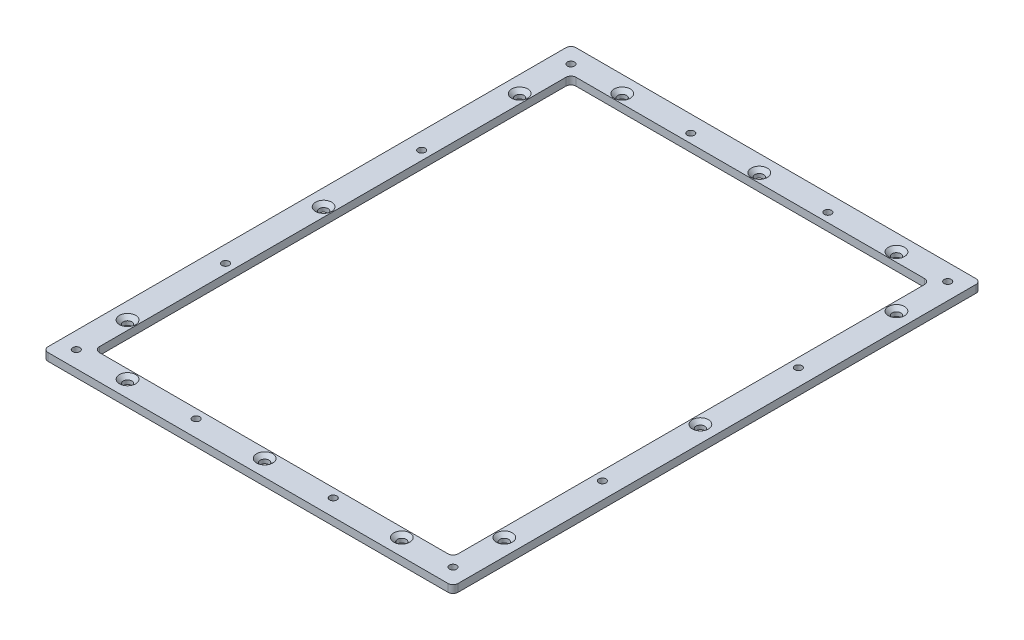
SolidWorks part; units mm, degrees
ref_plane "Front Plane" through (0, 0, 0) normal (0, 0, 1) x (1, 0, 0)
ref_plane "Top Plane" through (0, 0, 0) normal (0, 1, 0) x (1, 0, 0)
ref_plane "Right Plane" through (0, 0, 0) normal (1, 0, 0) x (0, 0, -1)
sketch "Sketch1" plane through (0, 0, 0) normal (0, 1, 0) x (1, 0, 0)
  line L0 (78, 103) -> (-78, 103) construction
  line L1 (-70, -93) -> (70, -93)
  line L2 (-70, -93) -> (-70, 93)
  line L3 (-70, 93) -> (70, 93)
  line L4 (70, -93) -> (70, 93)
  line L5 (-70, -93) -> (70, 93) construction
  line L6 (-70, 93) -> (70, -93) construction
  line L7 (80, -103) -> (-80, -103)
  line L8 (80, -103) -> (80, 103)
  line L9 (80, 103) -> (-80, 103)
  line L10 (-80, -103) -> (-80, 103)
  line L11 (80, -103) -> (-80, 103) construction
  line L12 (80, 103) -> (-80, -103) construction
  line L13 (-80, 101) -> (-80, -101) construction
  point P0 (0, 0)
  point P5 (0, 0)
  dimension "D1" = 10
  dimension "D2" = 10
extrude "Boss-Extrude1" add sketch "Sketch1" along normal blind 3
ref_axis "Axis2" through (0, -0.675, 0) along (0, 1, 0)
fillet "Fillet1" radius 2 8 edges at (80, 1.5, -103) (80, 1.5, 103) (-80, 1.5, -103) (-80, 1.5, 103) (70, 1.5, -93) (70, 1.5, 93) (-70, 1.5, 93) (-70, 1.5, -93)
ref_plane "Plane1" through (78, 0, 0) normal (-1, 0, 0) x (0, 0, 1)
sketch "Sketch6" plane through (0, 0, 0) normal (0, -1, 0) x (1, 0, 0)
  line L9 (-78, -102) -> (78, -102)
  line L10 (79, -101) -> (79, 101)
  line L11 (78, 102) -> (-78, 102)
  line L12 (-79, 101) -> (-79, -101)
  line L13 (-78, -102) -> (78, -102)
  line L14 (79, -101) -> (79, 101)
  line L15 (78, 102) -> (-78, 102)
  line L16 (-79, 101) -> (-79, -101)
  line L21 (-78, -101.5) -> (78, -101.5)
  line L22 (78.5, -101) -> (78.5, 101)
  line L23 (78, 101.5) -> (-78, 101.5)
  line L24 (-78.5, 101) -> (-78.5, -101)
  line L25 (-78, -101.5) -> (78, -101.5)
  line L26 (78.5, -101) -> (78.5, 101)
  line L27 (78, 101.5) -> (-78, 101.5)
  line L28 (-78.5, 101) -> (-78.5, -101)
  arc A8 (78, -102) -> (79, -101) centre (78, -101) ccw
  arc A9 (79, 101) -> (78, 102) centre (78, 101) ccw
  arc A10 (-78, 102) -> (-79, 101) centre (-78, 101) ccw
  arc A11 (-79, -101) -> (-78, -102) centre (-78, -101) ccw
  arc A12 (78, -102) -> (79, -101) centre (78, -101) ccw
  arc A13 (79, 101) -> (78, 102) centre (78, 101) ccw
  arc A14 (-78, 102) -> (-79, 101) centre (-78, 101) ccw
  arc A15 (-79, -101) -> (-78, -102) centre (-78, -101) ccw
  arc A20 (78, -101.5) -> (78.5, -101) centre (78, -101) ccw
  arc A21 (78, -101.5) -> (78.5, -101) centre (78, -101) ccw
  arc A22 (78.5, 101) -> (78, 101.5) centre (78, 101) ccw
  arc A23 (78.5, 101) -> (78, 101.5) centre (78, 101) ccw
  arc A24 (-78, 101.5) -> (-78.5, 101) centre (-78, 101) ccw
  arc A25 (-78, 101.5) -> (-78.5, 101) centre (-78, 101) ccw
  arc A26 (-78.5, -101) -> (-78, -101.5) centre (-78, -101) ccw
  arc A27 (-78.5, -101) -> (-78, -101.5) centre (-78, -101) ccw
  dimension "D1" = 1
  dimension "D2" = 1.5
extrude "Boss-Extrude3" add sketch "Sketch6" along normal blind 0.5
fillet "Fillet2" radius 0.25 32 edges at (-79, -0.5, 0) (-78.7071, -0.5, 101.7071) (0, -0.5, 102) (78.7071, -0.5, 101.7071) (79, -0.5, 0) (78.7071, -0.5, -101.7071) (0, -0.5, -102) (-78.5, -0.5, 0) (-78.3536, -0.5, 101.3536) (0, -0.5, 101.5) (78.3536, -0.5, 101.3536) (78.5, -0.5, 0) (78.3536, -0.5, -101.3536) (0, -0.5, -101.5) (-78.3536, 0, -101.3536) (-78.5, 0, 0) (-78.3536, 0, 101.3536) (0, 0, 101.5) (78.3536, 0, 101.3536) (78.5, 0, 0) (78.3536, 0, -101.3536) (-78.7071, 0, -101.7071) (-79, 0, 0) (-78.7071, 0, 101.7071) (0, 0, 102) (78.7071, 0, 101.7071) (79, 0, 0) (78.7071, 0, -101.7071) (-78.7071, -0.5, -101.7071) (-78.3536, -0.5, -101.3536) (0, 0, -101.5) (0, 0, -102)
sketch "Sketch10" plane through (0, 3, 0) normal (0, 1, 0) x (1, 0, 0)
  line L0 (-53.5, 96.5) -> (0, 96.5) construction
  line L1 (0, 96.5) -> (53.5, 96.5) construction
  line L2 (-73.5, 76.5) -> (-73.5, 0) construction
  line L3 (-73.5, 0) -> (-73.5, -76.5) construction
  line L4 (-53.5, -96.5) -> (0, -96.5) construction
  line L5 (0, -96.5) -> (53.5, -96.5) construction
  line L6 (73.5, 76.5) -> (73.5, 0) construction
  line L7 (73.5, 0) -> (73.5, -76.5) construction
  line L8 (-73.5, 76.5) -> (-73.5, 96.5) construction
  line L9 (-73.5, 96.5) -> (-53.5, 96.5) construction
  line L10 (0, 0) -> (0, 43.7963) construction
  line L11 (0, 0) -> (39.7562, 0) construction
  circle A0 centre (0, 96.5) radius 1.7 construction
  circle A1 centre (-53.5, 96.5) radius 1.7 construction
  circle A2 centre (-73.5, 76.5) radius 1.7 construction
  circle A3 centre (-73.5, 0) radius 1.7 construction
  circle A4 centre (-73.5, -76.5) radius 1.7 construction
  circle A5 centre (-53.5, -96.5) radius 1.7 construction
  circle A6 centre (0, -96.5) radius 1.7 construction
  circle A7 centre (53.5, -96.5) radius 1.7 construction
  circle A8 centre (73.5, -76.5) radius 1.7 construction
  circle A9 centre (73.5, 0) radius 1.7 construction
  circle A10 centre (73.5, 76.5) radius 1.7 construction
  circle A11 centre (53.5, 96.5) radius 1.7 construction
  circle A12 centre (0, 96.5) radius 1.7
  circle A13 centre (-53.5, 96.5) radius 1.7
  circle A14 centre (-73.5, 76.5) radius 1.7
  circle A15 centre (-73.5, 0) radius 1.7
  circle A16 centre (-73.5, -76.5) radius 1.7
  circle A17 centre (-53.5, -96.5) radius 1.7
  circle A18 centre (0, -96.5) radius 1.7
  circle A19 centre (53.5, -96.5) radius 1.7
  circle A20 centre (73.5, -76.5) radius 1.7
  circle A21 centre (73.5, 0) radius 1.7
  circle A22 centre (73.5, 76.5) radius 1.7
  circle A23 centre (53.5, 96.5) radius 1.7
  circle A24 centre (73.5, -38.25) radius 1.4
  circle A25 centre (73.5, 38.25) radius 1.4
  circle A26 centre (26.75, 96.5) radius 1.4
  circle A27 centre (-26.75, 96.5) radius 1.4
  circle A28 centre (-73.5, 38.25) radius 1.4
  circle A29 centre (-73.5, -38.25) radius 1.4
  circle A30 centre (-26.75, -96.5) radius 1.4
  circle A31 centre (26.75, -96.5) radius 1.4
  circle A32 centre (-73.5, 96.5) radius 1.4
  circle A33 centre (73.5, 96.5) radius 1.4
  circle A34 centre (73.5, -96.5) radius 1.4
  circle A35 centre (-73.5, -96.5) radius 1.4
  dimension "D1" = 2.8
extrude "Cut-Extrude1" cut sketch "Sketch10" against normal through all
hole_wizard "CSK for M3 Flat Head Machine Screw2" positions "3DSketch3" profile "Sketch11" countersink size "M3" standard "ANSI Metric" end condition through all
sketch3d "3DSketch3"
  line L0 (-53.5, 0, -96.5) -> (-53.5, 3, -96.5) construction
  line L1 (0, 0, -96.5) -> (0, 3, -96.5) construction
  line L2 (-73.5, 0, -76.5) -> (-73.5, 3, -76.5) construction
  line L3 (53.5, 0, -96.5) -> (53.5, 3, -96.5) construction
  line L4 (73.5, 0, -76.5) -> (73.5, 3, -76.5) construction
  line L5 (73.5, 0, 0) -> (73.5, 3, 0) construction
  line L6 (73.5, 0, 76.5) -> (73.5, 3, 76.5) construction
  line L7 (53.5, 0, 96.5) -> (53.5, 3, 96.5) construction
  line L8 (0, 0, 96.5) -> (0, 3, 96.5) construction
  line L9 (-53.5, 0, 96.5) -> (-53.5, 3, 96.5) construction
  line L10 (-73.5, 0, 76.5) -> (-73.5, 3, 76.5) construction
  line L11 (-73.5, 0, 0) -> (-73.5, 3, 0) construction
  point P0 (-53.5, 3, -96.5)
  point P4 (0, 3, -96.5)
  point P8 (-73.5, 3, -76.5)
  point P12 (53.5, 3, -96.5)
  point P16 (73.5, 3, -76.5)
  point P20 (73.5, 3, 0)
  point P28 (53.5, 3, 96.5)
  point P32 (0, 3, 96.5)
  point P36 (-53.5, 3, 96.5)
  point P40 (-73.5, 3, 76.5)
  point P44 (73.5, 3, 76.5)
  point P46 (-73.5, 3, 0)
sketch "Sketch11" plane through (-53.5, 3, -96.5) normal (1, 0, 0) x (0, 0, 1)
  line L0 (0, 0) -> (0, 3.5)
  line L1 (0, 3.5) -> (1.725, 3.5)
  line L2 (1.7, 3.475) -> (1.7, 1.45)
  line L3 (1.7, 1.45) -> (3.15, 0)
  line L5 (3.15, 0) -> (0, 0)
  line L6 (-1.7, 1.45) -> (-3.15, 0) construction
  line L7 (1.725, 3.5) -> (1.7, 3.475)
  line L8 (-1.725, 3.5) -> (-1.7, 3.475) construction
  line L11 (0, -6.35) -> (0, 107.95) construction
  dimension "Thru Hole Dia." = 3.4
  dimension "Thru Hole Depth" = 3.5
  dimension "Near C'Sink Dia." = 6.3
  dimension "Near C'Sink Angle" = 90
  dimension "Far C'Sink Dia." = 3.45
  dimension "Far C'Sink Angle" = 90
sketch "Sketch12" plane through (0, 0, 0) normal (0, -1, 0) x (1, 0, 0)
  line L0 (78, -102.25) -> (-78, -102.25) construction
  line L1 (79.25, 101) -> (79.25, -101) construction
  line L2 (-79.25, -101) -> (-79.25, 101) construction
  line L3 (-78, 102.25) -> (78, 102.25) construction
  line L4 (78, -102.25) -> (-78, -102.25)
  line L5 (79.25, 101) -> (79.25, -101)
  line L6 (-79.25, -101) -> (-79.25, 101)
  line L7 (-78, 102.25) -> (78, 102.25)
  line L9 (-249.5654, 283.7441) -> (249.5654, 283.7441)
  line L10 (-249.5654, 283.7441) -> (-249.5654, -283.7441)
  line L11 (-249.5654, -283.7441) -> (249.5654, -283.7441)
  line L12 (249.5654, 283.7441) -> (249.5654, -283.7441)
  line L13 (-249.5654, 283.7441) -> (249.5654, -283.7441) construction
  line L14 (-249.5654, -283.7441) -> (249.5654, 283.7441) construction
  arc A0 (-79.25, -101) -> (-78, -102.25) centre (-78, -101) ccw construction
  arc A1 (78, -102.25) -> (79.25, -101) centre (78, -101) ccw construction
  arc A2 (79.25, 101) -> (78, 102.25) centre (78, 101) ccw construction
  arc A3 (-78, 102.25) -> (-79.25, 101) centre (-78, 101) ccw construction
  arc A4 (-79.25, -101) -> (-78, -102.25) centre (-78, -101) ccw
  arc A5 (78, -102.25) -> (79.25, -101) centre (78, -101) ccw
  arc A6 (79.25, 101) -> (78, 102.25) centre (78, 101) ccw
  arc A7 (-78, 102.25) -> (-79.25, 101) centre (-78, 101) ccw
  point P4 (0, 0)
extrude "Cut-Extrude2" [suppressed] cut sketch "Sketch12" against normal through all
